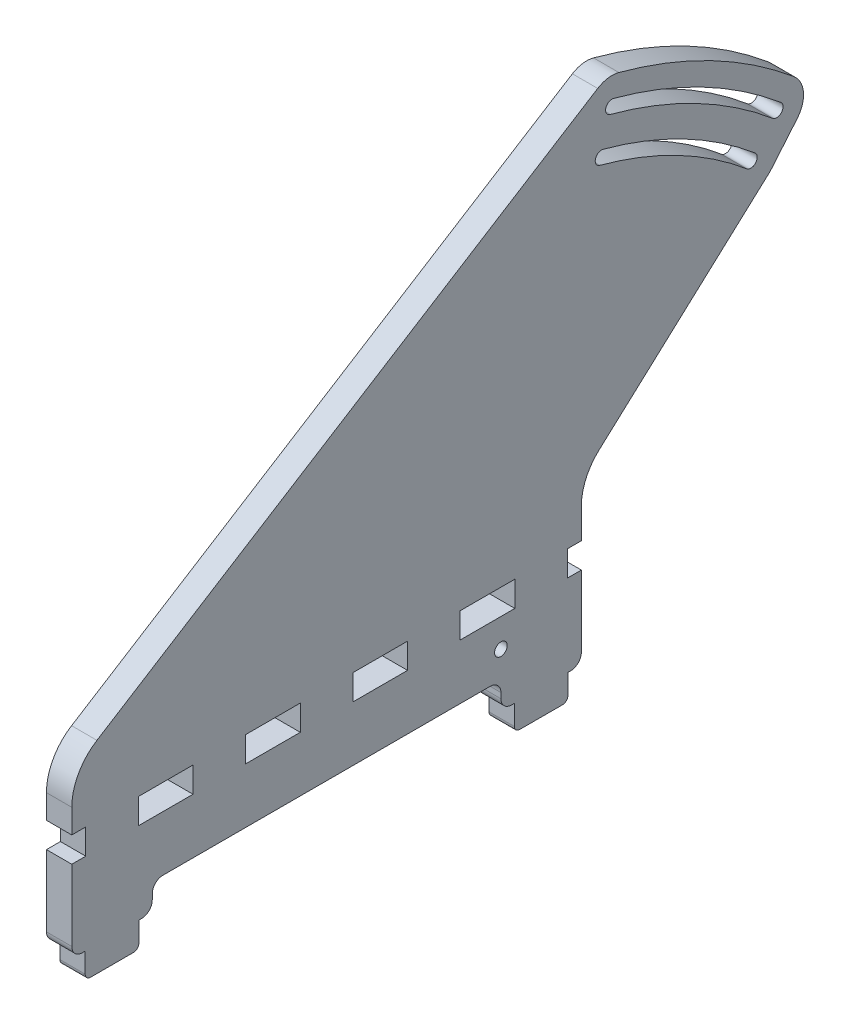
SolidWorks part; units mm, degrees
ref_plane "Front Plane" through (0, 0, 0) normal (0, 0, 1) x (1, 0, 0)
ref_plane "Top Plane" through (0, 0, 0) normal (0, 1, 0) x (1, 0, 0)
ref_plane "Right Plane" through (0, 0, 0) normal (1, 0, 0) x (0, 0, -1)
sketch "DriveBaseGeo"
  dimension "D1" = 6
  dimension "D2" = 6
  dimension "D5" = 203.2
  dimension "D3" = 25.4
  dimension "D4" = 25.4
  dimension "D8" = 25.4
  dimension "D9" = 25.4
  dimension "D6" = 9
  dimension "D7" = 9
sketch_block_instance "SlotOutline-1"
sketch_block "SlotOutline" parameters "D1"=12.7, "D2"=6
sketch_block_instance "SlotOutline-2"
sketch_block_instance "SlotOutline-3"
sketch_block_instance "SlotOutline-4"
sketch_block_instance "SlotOutline-5"
sketch_block_instance "SlotOutline-6"
sketch_block_instance "SlotOutline-7"
sketch_block_instance "SlotOutline-8"
sketch_block_instance "SlotOutline-9"
sketch_block_instance "SlotOutline-10"
sketch_block_instance "SlotOutline-11"
sketch_block_instance "SlotOutline-12"
sketch_block_instance "SlotOutline-13"
sketch_block_instance "SlotOutline-14"
sketch_block_instance "SlotOutline-15"
sketch_block_instance "SlotOutline-16"
sketch_block_instance "SlotOutline-17"
sketch_block_instance "SlotOutline-18"
sketch "Sketch2" plane through (0, 0, 0) normal (1, 0, 0) x (0, 0, -1)
  line L0 (-60.325, -47.8) -> (-60.325, -9.7)
  line L1 (-60.325, -9.7) -> (60.325, -9.7)
  line L2 (60.325, -9.7) -> (60.325, -47.8)
  line L3 (60.325, -47.8) -> (57.15, -47.8)
  line L4 (57.15, -47.8) -> (57.15, -53.8) construction
  line L5 (57.15, -53.8) -> (44.45, -53.8) construction
  line L6 (44.45, -53.8) -> (44.45, -47.8) construction
  line L7 (44.45, -47.8) -> (41.275, -47.8)
  line L8 (41.275, -47.8) -> (41.275, -41.45)
  line L9 (41.275, -41.45) -> (-41.275, -41.45)
  line L10 (-41.275, -41.45) -> (-41.275, -47.8)
  line L11 (-41.275, -47.8) -> (-44.45, -47.8)
  line L12 (-44.45, -47.8) -> (-44.45, -53.8) construction
  line L13 (-44.45, -53.8) -> (-57.15, -53.8) construction
  line L14 (-57.15, -53.8) -> (-57.15, -47.8) construction
  line L15 (-57.15, -47.8) -> (-60.325, -47.8)
  line L16 (-57.15, -47.8) -> (-44.45, -53.8) construction
  line L17 (44.45, -47.8) -> (57.15, -53.8) construction
  line L18 (57.15, -47.8) -> (44.45, -53.8) construction
  line L19 (-44.45, -47.8) -> (-57.15, -53.8) construction
  line L20 (101.6, -47.8) -> (-101.6, -47.8) construction
  line L21 (-41.275, -41.45) -> (-60.325, -41.45) construction
  line L22 (41.275, -41.45) -> (60.325, -41.45) construction
  line L23 (-60.325, -50.8) -> (-50.8, -50.8) construction
  line L24 (50.8, -50.8) -> (60.325, -50.8) construction
  line L25 (-57.15, -47.8) -> (-44.45, -47.8)
  line L26 (44.45, -47.8) -> (57.15, -47.8)
  line L27 (101.6, -22.4) -> (-101.6, -22.4) construction
  point P2 (50.8, -50.8)
  point P17 (-50.8, -50.8)
  dimension "D1" = 6.35
  dimension "D2" = 19.05
  dimension "D3" = 101.6
  dimension "D4" = 12.7
  dimension "D5" = 12.7
  dimension "D6" = 6
  dimension "D7" = 9.525
  dimension "D8" = 12.7
extrude "Mounting" add sketch "Sketch2" along normal mid plane 6
sketch "Sketch3" plane through (3, 0, 0) normal (1, 0, 0) x (0, 0, -1)
  line L0 (41.275, -35.1) -> (106.5822, 42.7301) construction
  line L3 (67.571, 63.0381) -> (41.275, -35.1) construction
  line L4 (41.275, -35.1) -> (160.1541, -35.1) construction
  line L6 (101.6, -47.8) -> (-101.6, -47.8) construction
  line L7 (60.325, -9.7) -> (60.325, -47.8) construction
  line L8 (64.1965, 68.4172) -> (-60.325, -9.7)
  line L9 (-60.325, -9.7) -> (60.325, -9.7)
  line L10 (111.4466, 38.6484) -> (105.3241, 31.3518)
  line L11 (105.3241, 31.3518) -> (100.4597, 35.4335) construction
  line L12 (104.7349, 30.7384) -> (60.325, -9.7)
  arc A0 (110.6639, 47.5945) -> (69.2145, 69.1717) centre (41.275, -35.1) ccw
  arc A1 (106.5822, 42.7301) -> (67.571, 63.0381) centre (41.275, -35.1) ccw construction
  arc A2 (107.5464, 43.8792) -> (67.9592, 64.487) centre (41.275, -35.1) ccw
  arc A3 (105.618, 41.581) -> (67.1828, 61.5892) centre (41.275, -35.1) ccw
  arc A4 (105.618, 41.581) -> (107.5464, 43.8792) centre (106.5822, 42.7301) ccw
  arc A5 (67.9592, 64.487) -> (67.1828, 61.5892) centre (67.571, 63.0381) ccw
  arc A6 (110.6639, 47.5945) -> (111.4466, 38.6484) centre (106.5822, 42.7301) cw
  arc A7 (69.2145, 69.1717) -> (64.1965, 68.4172) centre (67.571, 63.0381) ccw
  circle A8 centre (41.275, -35.1) radius 1.5
  arc A9 (100.4597, 35.4335) -> (65.1058, 53.8376) centre (41.275, -35.1) ccw construction
  arc A10 (101.4239, 36.5826) -> (65.494, 55.2865) centre (41.275, -35.1) ccw
  arc A11 (99.4955, 34.2845) -> (64.7175, 52.3887) centre (41.275, -35.1) ccw
  arc A12 (99.4955, 34.2845) -> (101.4239, 36.5826) centre (100.4597, 35.4335) ccw
  arc A13 (65.494, 55.2865) -> (64.7175, 52.3887) centre (65.1058, 53.8376) ccw
  arc A14 (105.3241, 31.3518) -> (104.7349, 30.7384) centre (100.4597, 35.4335) cw
  point P5 (88.1887, 55.0203)
  point P21 (41.275, -35.1)
  point P27 (83.7905, 46.5715)
  point P34 (60.85, -9.7)
  dimension "D1" = 3
  dimension "D4" = 6.35
  dimension "D8" = 3
  dimension "D2" = 25
  dimension "D3" = 50
  dimension "D5" = 101.6
  dimension "D6" = 12.7
  dimension "D7" = 19.05
  dimension "D9" = 9.525
extrude "Boss-Extrude2" add sketch "Sketch3" against normal up to surface (6 mm away) up to face at (-3, -36.6875, 0)
extrude "PivotHole" cut sketch "Sketch3<2>" against normal through all both and the other way through all contours A8 region at (3, -35.1, -41.275)
sketch "Sketch3<2>" plane through (3, 0, 0) normal (1, 0, 0) x (0, 0, -1) same geometry as "Sketch3"
sketch "Sketch4" plane through (0, -47.8, 0) normal (0, -1, 0) x (1, 0, 0)
  line L0 (-3, -41.275) -> (-3, -60.325) construction
  line L1 (-3, -60.325) -> (3, -60.325) construction
  line L2 (3, -60.325) -> (3, -41.275) construction
  line L3 (3, -41.275) -> (-3, -41.275) construction
  line L4 (-3, 60.325) -> (-3, 41.275) construction
  line L5 (-3, 41.275) -> (3, 41.275) construction
  line L6 (3, 41.275) -> (3, 60.325) construction
  line L7 (3, 60.325) -> (-3, 60.325) construction
  line L8 (-3, -41.275) -> (-3, -60.325) construction
  line L9 (-3, -60.325) -> (3, -60.325) construction
  line L10 (3, -60.325) -> (3, -41.275) construction
  line L11 (3, -41.275) -> (-3, -41.275) construction
  line L12 (-3, 60.325) -> (-3, 41.275) construction
  line L13 (-3, 41.275) -> (3, 41.275) construction
  line L14 (3, 41.275) -> (3, 60.325) construction
  line L15 (3, 60.325) -> (-3, 60.325) construction
  line L16 (-3, 60.325) -> (3, 41.275) construction
  line L17 (3, 60.325) -> (-3, 41.275) construction
  line L18 (-3, -41.275) -> (3, -60.325) construction
  line L19 (3, -41.275) -> (-3, -60.325) construction
  line L21 (-3, 44.45) -> (3, 44.45)
  line L22 (-3, 44.45) -> (-3, 57.15)
  line L23 (-3, 57.15) -> (3, 57.15)
  line L24 (3, 44.45) -> (3, 57.15)
  line L25 (-3, 44.45) -> (3, 57.15) construction
  line L26 (-3, 57.15) -> (3, 44.45) construction
  line L27 (-3, -57.15) -> (3, -57.15)
  line L28 (-3, -57.15) -> (-3, -44.45)
  line L29 (-3, -44.45) -> (3, -44.45)
  line L30 (3, -57.15) -> (3, -44.45)
  line L31 (-3, -57.15) -> (3, -44.45) construction
  line L32 (-3, -44.45) -> (3, -57.15) construction
  point P6 (0, -50.8)
  point P9 (0, 50.8)
  point P10 (0, 50.8)
  point P15 (0, -50.8)
  dimension "D1" = 12.7
extrude "Tab" add sketch "Sketch4" along normal blind 6
fillet "Fillet1" radius 12.7 2 edges at (0, -9.7, 60.325) (0, -9.7, -60.325)
fillet "Fillet2" radius 2.54 6 edges at (0, -47.8, -60.325) (0, -47.8, -41.275) (0, -41.45, 41.275) (0, -47.8, 41.275) (0, -47.8, 60.325) (0, -41.45, -41.275)
fillet "TabFillet" radius 1.27 4 edges at (0, -53.8, -57.15) (0, -53.8, -44.45) (0, -53.8, 44.45) (0, -53.8, 57.15)
sketch "Sketch5" plane through (3, 0, 0) normal (1, 0, 0) x (0, 0, -1)
  line L0 (101.6, -22.4) -> (-101.6, -22.4) construction
  line L1 (-82.423, -28.4) -> (-95.377, -28.4)
  line L2 (-82.423, -28.4) -> (-82.423, -22.4)
  line L3 (-82.423, -22.4) -> (-95.377, -22.4)
  line L4 (-95.377, -28.4) -> (-95.377, -22.4)
  line L5 (-82.423, -28.4) -> (-95.377, -22.4) construction
  line L6 (-82.423, -22.4) -> (-95.377, -28.4) construction
  line L7 (101.6, -28.4) -> (-101.6, -28.4) construction
  line L8 (-95.25, -28.4) -> (-82.55, -22.4) construction
  line L9 (-57.023, -28.4) -> (-69.977, -28.4)
  line L10 (-57.023, -28.4) -> (-57.023, -22.4)
  line L11 (-69.977, -28.4) -> (-69.977, -22.4)
  line L12 (-57.023, -28.4) -> (-69.977, -22.4) construction
  line L13 (-57.023, -22.4) -> (-69.977, -28.4) construction
  line L14 (-57.023, -22.4) -> (-69.977, -22.4)
  line L15 (-31.623, -28.4) -> (-44.577, -28.4)
  line L16 (-31.623, -28.4) -> (-31.623, -22.4)
  line L17 (-44.577, -28.4) -> (-44.577, -22.4)
  line L18 (-31.623, -28.4) -> (-44.577, -22.4) construction
  line L19 (-31.623, -22.4) -> (-44.577, -28.4) construction
  line L20 (-31.623, -22.4) -> (-44.577, -22.4)
  line L21 (-6.223, -28.4) -> (-19.177, -28.4)
  line L22 (-6.223, -28.4) -> (-6.223, -22.4)
  line L23 (-19.177, -28.4) -> (-19.177, -22.4)
  line L24 (-6.223, -28.4) -> (-19.177, -22.4) construction
  line L25 (-6.223, -22.4) -> (-19.177, -28.4) construction
  line L26 (-6.223, -22.4) -> (-19.177, -22.4)
  line L27 (19.177, -28.4) -> (6.223, -28.4)
  line L28 (19.177, -28.4) -> (19.177, -22.4)
  line L29 (6.223, -28.4) -> (6.223, -22.4)
  line L30 (19.177, -28.4) -> (6.223, -22.4) construction
  line L31 (19.177, -22.4) -> (6.223, -28.4) construction
  line L32 (19.177, -22.4) -> (6.223, -22.4)
  line L33 (44.577, -28.4) -> (31.623, -28.4)
  line L34 (44.577, -28.4) -> (44.577, -22.4)
  line L35 (31.623, -28.4) -> (31.623, -22.4)
  line L36 (44.577, -28.4) -> (31.623, -22.4) construction
  line L37 (44.577, -22.4) -> (31.623, -28.4) construction
  line L38 (44.577, -22.4) -> (31.623, -22.4)
  line L39 (69.977, -28.4) -> (57.023, -28.4)
  line L40 (69.977, -28.4) -> (69.977, -22.4)
  line L41 (57.023, -28.4) -> (57.023, -22.4)
  line L42 (69.977, -28.4) -> (57.023, -22.4) construction
  line L43 (69.977, -22.4) -> (57.023, -28.4) construction
  line L44 (69.977, -22.4) -> (57.023, -22.4)
  line L45 (95.377, -28.4) -> (82.423, -28.4)
  line L46 (95.377, -28.4) -> (95.377, -22.4)
  line L47 (82.423, -28.4) -> (82.423, -22.4)
  line L48 (95.377, -28.4) -> (82.423, -22.4) construction
  line L49 (95.377, -22.4) -> (82.423, -28.4) construction
  line L50 (95.377, -22.4) -> (82.423, -22.4)
  point P0 (-88.9, -25.4)
  point P18 (-63.5, -25.4)
  dimension "D2" = 25.4
  dimension "D3" = 12.446
  dimension "D1" = 8
extrude "Cut-Extrude2" cut sketch "Sketch5" against normal through all both and the other way through all
equation "\"SlotPitch\"=1"
equation "\"D8@DriveBaseGeo\" = \"SlotPitch\""
equation "\"D9@DriveBaseGeo\" = \"SlotPitch\""
